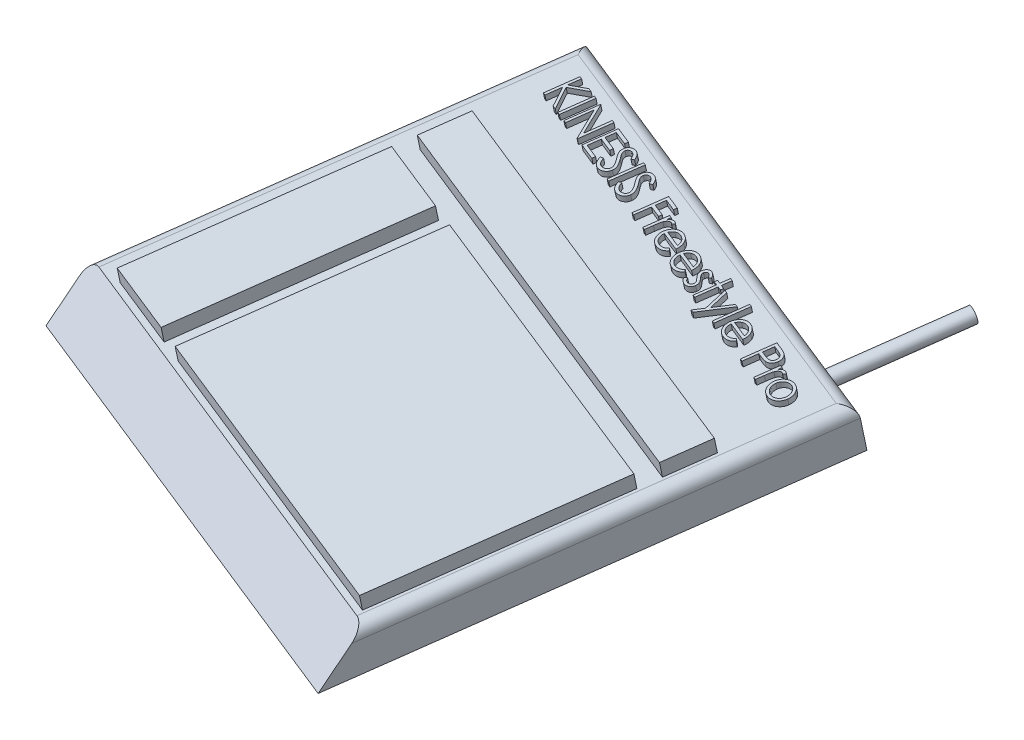
SolidWorks part; units mm, degrees
ref_plane "Front Plane" through (0, 0, 0) normal (0, 0, 1) x (1, 0, 0)
ref_plane "Top Plane" through (0, 0, 0) normal (0, 1, 0) x (1, 0, 0)
ref_plane "Right Plane" through (0, 0, 0) normal (1, 0, 0) x (0, 0, -1)
sketch "Sketch1" plane through (0, 0, 0) normal (0, 1, 0) x (1, 0, 0)
  line L1 (0, 0) -> (196.85, 0)
  line L2 (0, 0) -> (0, -165.1)
  line L3 (0, -165.1) -> (196.85, -165.1)
  line L4 (196.85, 0) -> (196.85, -165.1)
  dimension "D1" = 165.1
  dimension "D3" = 196.85
extrude "Boss-Extrude1" add sketch "Sketch1" along normal blind 19.05
sketch "Sketch2" plane through (0, 0, 0) normal (0, 1, 0) x (1, 0, 0)
  line L0 (0, -165.1) -> (196.85, -165.1)
  line L1 (0, -165.1) -> (0, -190.5)
  line L2 (196.85, -165.1) -> (196.85, -190.5)
  line L3 (0, -190.5) -> (196.85, -190.5)
  dimension "D1" = 25.4
extrude "Boss-Extrude2" add sketch "Sketch2" along normal blind 19.05 contours L0 L1 L3 L2
chamfer "Chamfer1" distance 19.05 angle 45 1 edges at (98.425, 19.05, 190.5)
sketch "Sketch3" plane through (0, 19.05, 0) normal (0, 1, 0) x (1, 0, 0)
  line L0 (196.85, -171.45) -> (196.85, 0) construction
  line L1 (15.24, -168.91) -> (46.99, -168.91)
  line L2 (15.24, -168.91) -> (15.24, -73.66)
  line L3 (15.24, -73.66) -> (46.99, -73.66)
  line L4 (46.99, -168.91) -> (46.99, -73.66)
  line L5 (57.15, -168.91) -> (190.5, -168.91)
  line L6 (57.15, -168.91) -> (57.15, -73.66)
  line L7 (57.15, -73.66) -> (190.5, -73.66)
  line L8 (190.5, -168.91) -> (190.5, -73.66)
  line L9 (0, -171.45) -> (196.85, -171.45) construction
  line L10 (0, 0) -> (0, -171.45) construction
  line L11 (15.24, -45.72) -> (190.5, -45.72)
  line L12 (15.24, -45.72) -> (15.24, -64.77)
  line L13 (15.24, -64.77) -> (190.5, -64.77)
  line L14 (190.5, -45.72) -> (190.5, -64.77)
  dimension "D1" = 6.35
  dimension "D2" = 133.35
  dimension "D3" = 2.54
  dimension "D4" = 95.25
  dimension "D5" = 2.54
  dimension "D6" = 31.75
  dimension "D7" = 10.16
  dimension "D8" = 95.25
  dimension "D9" = 6.35
  dimension "D10" = 15.24
  dimension "D11" = 8.89
  dimension "D12" = 19.05
extrude "Boss-Extrude3" add sketch "Sketch3" along normal blind 6.35
sketch "Sketch4" plane through (0, 19.05, 0) normal (0, 1, 0) x (1, 0, 0)
  line L0 (15.24, -45.72) -> (15.24, -64.77) construction
  text T0 "KINESIS Freestyle Pro" font "Century Gothic" height 12.7
  dimension "D1" = 0
extrude "Boss-Extrude4" add sketch "Sketch4" along normal blind 2.54
sketch "Sketch5" plane through (0, 0, 0) normal (0, 0, -1) x (-1, 0, 0)
  line L0 (-196.85, 19.05) -> (0, 19.05) construction
  line L1 (-196.85, 19.05) -> (-196.85, 0) construction
  circle A0 centre (-171.45, 10.16) radius 3.175
  dimension "D3" = 6.35
  dimension "D1" = 8.89
  dimension "D2" = 25.4
extrude "Boss-Extrude5" add sketch "Sketch5" along normal blind 50.8
fillet "Fillet1" radius 5.08 3 edges at (98.425, 19.05, 0) (0, 19.05, 85.725) (196.85, 19.05, 85.725)
sketch "Sketch6" plane through (0, 0, 0) normal (0, -1, 0) x (1, 0, 0)
  line L0 (25.4, 179.07) -> (12.7, 179.07) construction
  line L1 (25.4, 172.72) -> (12.7, 172.72)
  line L2 (25.4, 185.42) -> (12.7, 185.42)
  line L3 (0, 190.5) -> (196.85, 190.5) construction
  line L4 (0, 0) -> (0, 190.5) construction
  line L5 (98.425, 190.5) -> (98.425, 55.114) construction
  line L6 (0, 95.25) -> (246.7978, 95.25) construction
  line L7 (171.45, 179.07) -> (184.15, 179.07) construction
  line L8 (171.45, 172.72) -> (184.15, 172.72)
  line L9 (171.45, 185.42) -> (184.15, 185.42)
  line L10 (171.45, 11.43) -> (184.15, 11.43) construction
  line L11 (171.45, 17.78) -> (184.15, 17.78)
  line L12 (171.45, 5.08) -> (184.15, 5.08)
  line L13 (25.4, 11.43) -> (12.7, 11.43) construction
  line L14 (25.4, 17.78) -> (12.7, 17.78)
  line L15 (25.4, 5.08) -> (12.7, 5.08)
  arc A0 (25.4, 172.72) -> (25.4, 185.42) centre (25.4, 179.07) ccw
  arc A1 (12.7, 185.42) -> (12.7, 172.72) centre (12.7, 179.07) ccw
  arc A2 (171.45, 172.72) -> (171.45, 185.42) centre (171.45, 179.07) cw
  arc A3 (184.15, 185.42) -> (184.15, 172.72) centre (184.15, 179.07) cw
  arc A4 (171.45, 17.78) -> (171.45, 5.08) centre (171.45, 11.43) ccw
  arc A5 (184.15, 5.08) -> (184.15, 17.78) centre (184.15, 11.43) ccw
  arc A6 (25.4, 17.78) -> (25.4, 5.08) centre (25.4, 11.43) cw
  arc A7 (12.7, 5.08) -> (12.7, 17.78) centre (12.7, 11.43) cw
  point P2 (19.05, 179.07)
  point P17 (177.8, 179.07)
  point P24 (177.8, 11.43)
  point P31 (19.05, 11.43)
  dimension "D1" = 6.35
  dimension "D2" = 12.7
  dimension "D3" = 5.08
  dimension "D4" = 19.05
extrude "Boss-Extrude6" add sketch "Sketch6" along normal blind 2.54
move or copy body "Body-Move/Copy1" bodies to move or copy 106 copy no rotation origin (9.411, -14.3523, 189.9256) rotation axis (0.5099, -0.8555, -0.0899) rotation angle 23.292
move or copy body "Body-Move/Copy2" bodies to move or copy 107 copy no translate (0, 15.24, -33.02)
move or copy body "Body-Move/Copy3" bodies to move or copy 108 copy no translate (0, 10.16, 0)
